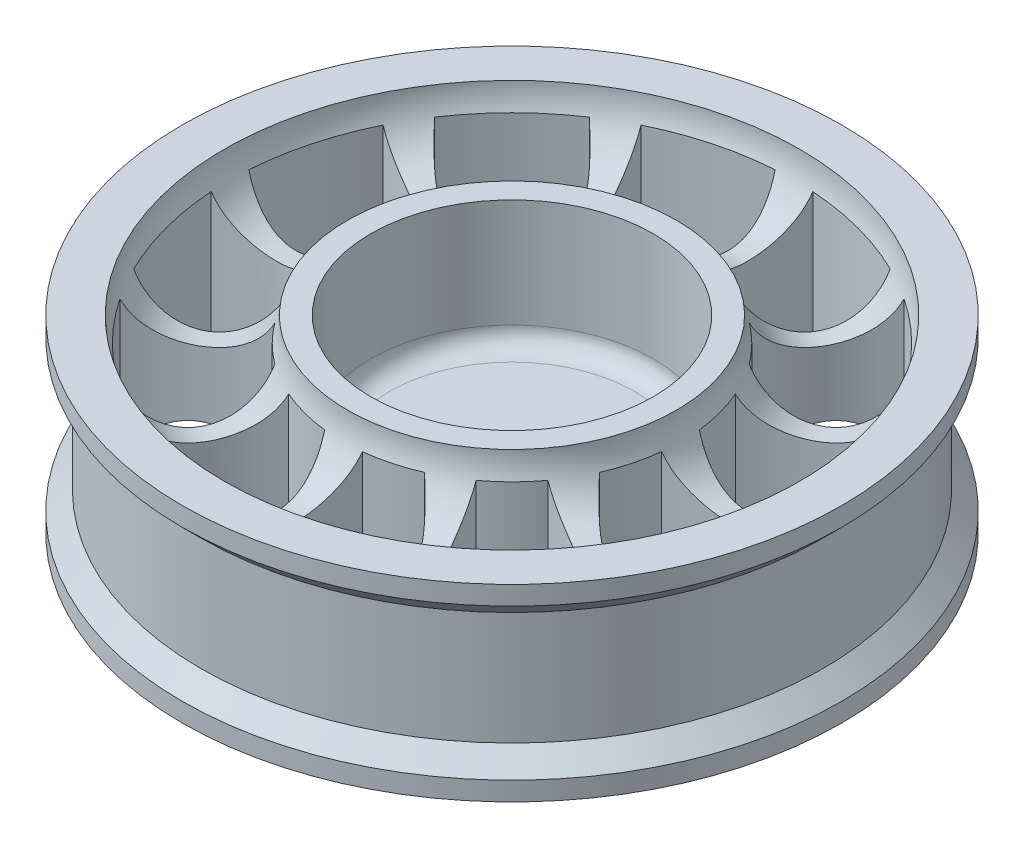
SolidWorks part; units mm, degrees
ref_plane "Front Plane" through (0, 0, 0) normal (0, 0, 1) x (1, 0, 0)
ref_plane "Top Plane" through (0, 0, 0) normal (0, 1, 0) x (1, 0, 0)
ref_plane "Right Plane" through (0, 0, 0) normal (1, 0, 0) x (0, 0, -1)
sketch "Sketch2" plane through (0, 0, 0) normal (0, 1, 0) x (1, 0, 0)
  circle A1 centre (0, 0) radius 35
  dimension "D2" = 70
extrude "Boss-Extrude1" add sketch "Sketch2" along normal blind 20
sketch "Sketch3" plane through (0, 20, 0) normal (0, 1, 0) x (1, 0, 0)
  circle A0 centre (0, 0) radius 15
  dimension "D1" = 30
extrude "Cut-Extrude1" cut sketch "Sketch3" against normal offset from surface (13.5 mm away) 6.5 up to face at (0, 0, 35)
sketch "Sketch4" plane through (0, 0, 0) normal (0, -1, 0) x (1, 0, 0)
  circle A0 centre (0, 0) radius 1.35
  point P3 (2.54, 0)
  dimension "D1" = 2.7
extrude "Cut-Extrude2" cut sketch "Sketch4" against normal through all
sketch "Sketch5" plane through (0, 0, 0) normal (0, -1, 0) x (1, 0, 0)
  line L1 (2.54, 0) -> (1.27, 2.1997)
  line L2 (1.27, 2.1997) -> (-1.27, 2.1997)
  line L3 (-1.27, 2.1997) -> (-2.54, 0)
  line L4 (-2.54, 0) -> (-1.27, -2.1997)
  line L5 (-1.27, -2.1997) -> (1.27, -2.1997)
  line L6 (1.27, -2.1997) -> (2.54, 0)
  circle A0 centre (0, 0) radius 2.1997 construction
  dimension "D1" = 2.54
extrude "Cut-Extrude3" cut sketch "Sketch5" against normal blind 5
ref_plane "Plane1" through (0, 10, 0) normal (0, 1, 0) x (1, 0, 0)
sketch "Sketch6" plane through (0, 10, 0) normal (0, 1, 0) x (1, 0, 0)
  circle A1 centre (0, 0) radius 33
  circle A2 centre (0, 0) radius 35
  circle A3 centre (0, 0) radius 35
  dimension "D1" = 0
  dimension "D2" = 2
extrude "Cut-Extrude5" cut sketch "Sketch6" against normal mid plane 16 contours A3 | A1
sketch "Sketch8" plane through (0, 20, 0) normal (0, 1, 0) x (1, 0, 0)
  circle A0 centre (0, 0) radius 15 construction
  circle A1 centre (0, 0) radius 15 construction
  circle A2 centre (0, 0) radius 18
  circle A3 centre (0, 0) radius 35 construction
  circle A4 centre (0, 0) radius 35 construction
  circle A5 centre (0, 0) radius 30
  circle M2 centre (0, 0) radius 15
  dimension "D2" = 5
  dimension "D1" = 3
extrude "Cut-Extrude8" cut sketch "Sketch8" against normal up to next contours A5 A2 | M2 | A2 M2
sketch "Sketch11" plane through (0, 0, 0) normal (0, -1, 0) x (1, 0, 0)
  line L0 (0, 0) -> (0, 11.5921) construction
  line L1 (-2, 29.9333) -> (-2, 17.8885) construction
  circle A0 centre (0, 0) radius 30 construction
  circle A1 centre (0, 0) radius 18
  arc A2 (2, 17.8885) -> (-2, 17.8885) centre (0, 0) ccw
  arc A3 (2, 29.9333) -> (-2, 29.9333) centre (0, 0) ccw
  arc A4 (10.6763, 14.4919) -> (7.2122, 16.4919) centre (0, 0) ccw
  arc A5 (16.6987, 24.923) -> (13.2346, 26.923) centre (0, 0) ccw
  arc A6 (16.4919, 7.2122) -> (14.4919, 10.6763) centre (0, 0) ccw
  arc A7 (26.923, 13.2346) -> (24.923, 16.6987) centre (0, 0) ccw
  arc A8 (17.8885, -2) -> (17.8885, 2) centre (0, 0) ccw
  arc A9 (29.9333, -2) -> (29.9333, 2) centre (0, 0) ccw
  arc A10 (14.4919, -10.6763) -> (16.4919, -7.2122) centre (0, 0) ccw
  arc A11 (24.923, -16.6987) -> (26.923, -13.2346) centre (0, 0) ccw
  arc A12 (7.2122, -16.4919) -> (10.6763, -14.4919) centre (0, 0) ccw
  arc A13 (13.2346, -26.923) -> (16.6987, -24.923) centre (0, 0) ccw
  arc A14 (-2, -17.8885) -> (2, -17.8885) centre (0, 0) ccw
  arc A15 (-2, -29.9333) -> (2, -29.9333) centre (0, 0) ccw
  arc A16 (-10.6763, -14.4919) -> (-7.2122, -16.4919) centre (0, 0) ccw
  arc A17 (-16.6987, -24.923) -> (-13.2346, -26.923) centre (0, 0) ccw
  arc A18 (-16.4919, -7.2122) -> (-14.4919, -10.6763) centre (0, 0) ccw
  arc A19 (-26.923, -13.2346) -> (-24.923, -16.6987) centre (0, 0) ccw
  arc A20 (-17.8885, 2) -> (-17.8885, -2) centre (0, 0) ccw
  arc A21 (-29.9333, 2) -> (-29.9333, -2) centre (0, 0) ccw
  arc A22 (-14.4919, 10.6763) -> (-16.4919, 7.2122) centre (0, 0) ccw
  arc A23 (-24.923, 16.6987) -> (-26.923, 13.2346) centre (0, 0) ccw
  arc A24 (-7.2122, 16.4919) -> (-10.6763, 14.4919) centre (0, 0) ccw
  arc A25 (-13.2346, 26.923) -> (-16.6987, 24.923) centre (0, 0) ccw
  spline S0 degree 2 poles (-2, 29.9333) (0, 23.9109) (-2, 17.8885) knots 0 0 0 1 1 1
  spline S1 degree 2 poles (2, 29.9333) (0, 23.9109) (2, 17.8885) knots 0 0 0 1 1 1
  spline S2 degree 2 poles (13.2346, 26.923) (11.9555, 20.7074) (7.2122, 16.4919) knots 0 0 0 1 1 1
  spline S3 degree 2 poles (16.6987, 24.923) (11.9555, 20.7074) (10.6763, 14.4919) knots 0 0 0 1 1 1
  spline S4 degree 2 poles (24.923, 16.6987) (20.7074, 11.9555) (14.4919, 10.6763) knots 0 0 0 1 1 1
  spline S5 degree 2 poles (26.923, 13.2346) (20.7074, 11.9555) (16.4919, 7.2122) knots 0 0 0 1 1 1
  spline S6 degree 2 poles (29.9333, 2) (23.9109, 0) (17.8885, 2) knots 0 0 0 1 1 1
  spline S7 degree 2 poles (29.9333, -2) (23.9109, 0) (17.8885, -2) knots 0 0 0 1 1 1
  spline S8 degree 2 poles (26.923, -13.2346) (20.7074, -11.9555) (16.4919, -7.2122) knots 0 0 0 1 1 1
  spline S9 degree 2 poles (24.923, -16.6987) (20.7074, -11.9555) (14.4919, -10.6763) knots 0 0 0 1 1 1
  spline S10 degree 2 poles (16.6987, -24.923) (11.9555, -20.7074) (10.6763, -14.4919) knots 0 0 0 1 1 1
  spline S11 degree 2 poles (13.2346, -26.923) (11.9555, -20.7074) (7.2122, -16.4919) knots 0 0 0 1 1 1
  spline S12 degree 2 poles (2, -29.9333) (0, -23.9109) (2, -17.8885) knots 0 0 0 1 1 1
  spline S13 degree 2 poles (-2, -29.9333) (0, -23.9109) (-2, -17.8885) knots 0 0 0 1 1 1
  spline S14 degree 2 poles (-13.2346, -26.923) (-11.9555, -20.7074) (-7.2122, -16.4919) knots 0 0 0 1 1 1
  spline S15 degree 2 poles (-16.6987, -24.923) (-11.9555, -20.7074) (-10.6763, -14.4919) knots 0 0 0 1 1 1
  spline S16 degree 2 poles (-24.923, -16.6987) (-20.7074, -11.9555) (-14.4919, -10.6763) knots 0 0 0 1 1 1
  spline S17 degree 2 poles (-26.923, -13.2346) (-20.7074, -11.9555) (-16.4919, -7.2122) knots 0 0 0 1 1 1
  spline S18 degree 2 poles (-29.9333, -2) (-23.9109, 0) (-17.8885, -2) knots 0 0 0 1 1 1
  spline S19 degree 2 poles (-29.9333, 2) (-23.9109, 0) (-17.8885, 2) knots 0 0 0 1 1 1
  spline S20 degree 2 poles (-26.923, 13.2346) (-20.7074, 11.9555) (-16.4919, 7.2122) knots 0 0 0 1 1 1
  spline S21 degree 2 poles (-24.923, 16.6987) (-20.7074, 11.9555) (-14.4919, 10.6763) knots 0 0 0 1 1 1
  spline S22 degree 2 poles (-16.6987, 24.923) (-11.9555, 20.7074) (-10.6763, 14.4919) knots 0 0 0 1 1 1
  spline S23 degree 2 poles (-13.2346, 26.923) (-11.9555, 20.7074) (-7.2122, 16.4919) knots 0 0 0 1 1 1
  point P11 (-2, 23.9109)
  point P81 (0, 0)
  dimension "D4" = 12
  dimension "D1" = 0
  dimension "D2" = 2
  dimension "2" = 1
  dimension "D3" = 2
extrude "Boss-Extrude2" add sketch "Sketch11" against normal up to surface (20 mm away) up to face at (0, 20, 30)
sketch "Sketch12" plane through (0, 0, 0) normal (0, -1, 0) x (-1, 0, 0)
  circle A0 centre (0, 0) radius 24
  dimension "D1" = 48
sweep "Cut-Sweep1" cut path "Sketch12" circular profile diameter 13.0755 parameters "D3"=13.0755
mirror "Mirror1" about plane through (0, 10, 0) normal (0, 1, 0) of "Cut-Sweep1"
fillet "Fillet1" radius 2 1 edges at (0, 6.5, 15)
chamfer "Chamfer1" distance 2 angle 45 2 edges at (0, 18, 33) (0, 2, 33)
